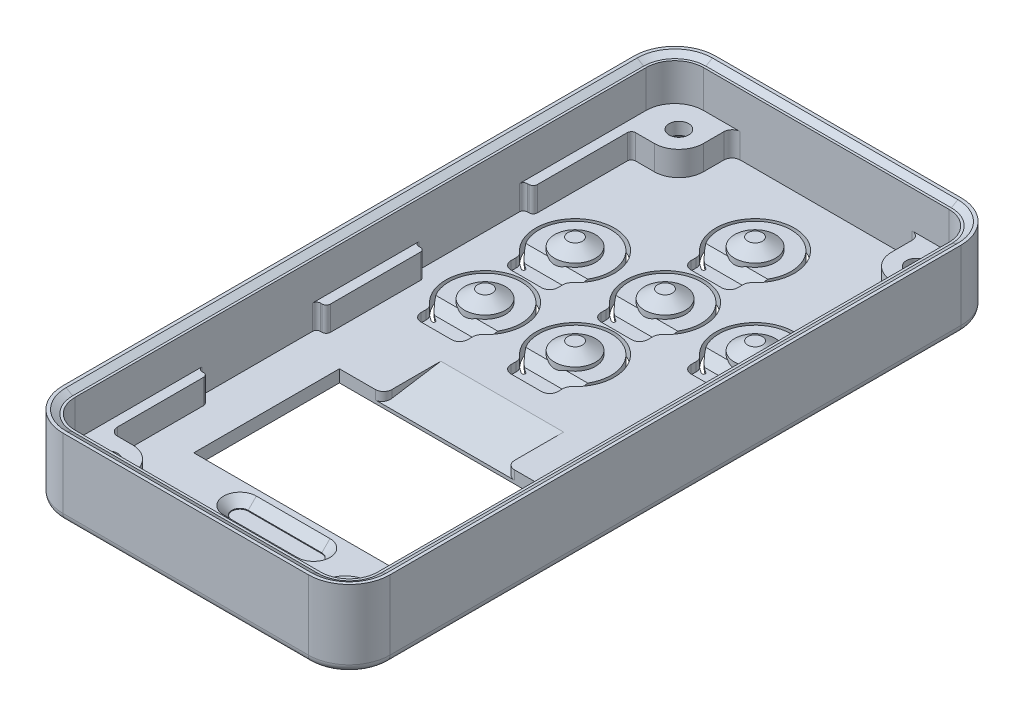
SolidWorks part; units mm, degrees
ref_plane "Front Plane" through (0, 0, 0) normal (0, 0, 1) x (1, 0, 0)
ref_plane "Top Plane" through (0, 0, 0) normal (0, 1, 0) x (1, 0, 0)
ref_plane "Right Plane" through (0, 0, 0) normal (1, 0, 0) x (0, 0, -1)
sketch "Base Sketch" plane through (0, 0, 0) normal (0, 1, 0) x (1, 0, 0)
  line L0 (0, 0) -> (40, 0)
  line L1 (40, 0) -> (40, 79.79)
  line L2 (40, 79.79) -> (0, 79.79)
  line L3 (0, 79.79) -> (0, 0)
extrude "Base" add sketch "Base Sketch" along normal blind 9.5
fillet "Corner Rounds R5" radius 5 4 edges at (0, 4.75, -79.79) (40, 4.75, -79.79) (40, 4.75, 0) (0, 4.75, 0)
shell "Shell 1.5" thickness 1.5 removed face at (20, 9.5, -39.895)
sketch "Boss Sketch" plane through (0, 0, 0) normal (0, 1, 0) x (1, 0, 0)
  line L0 (1.5, 1.5) -> (8.5, 1.5)
  line L1 (8.5, 1.5) -> (8.5, 5)
  line L2 (5.5, 8) -> (1.5, 8)
  line L3 (1.5, 8) -> (1.5, 1.5)
  line L4 (38.5, 1.5) -> (31.5, 1.5)
  line L5 (31.5, 1.5) -> (31.5, 5)
  line L6 (34.5, 8) -> (38.5, 8)
  line L7 (38.5, 8) -> (38.5, 1.5)
  line L16 (1.5, 78.29) -> (8.5, 78.29)
  line L17 (8.5, 78.29) -> (8.5, 74.79)
  line L18 (5.5, 71.79) -> (1.5, 71.79)
  line L19 (1.5, 71.79) -> (1.5, 78.29)
  line L20 (38.5, 78.29) -> (31.5, 78.29)
  line L21 (31.5, 78.29) -> (31.5, 74.79)
  line L22 (34.5, 71.79) -> (38.5, 71.79)
  line L23 (38.5, 71.79) -> (38.5, 78.29)
  arc A0 (8.5, 5) -> (5.5, 8) centre (5.4999, 4.9999) ccw
  circle A1 centre (5.5, 5) radius 1
  arc A2 (31.5, 5) -> (34.5, 8) centre (34.5001, 4.9999) cw
  circle A3 centre (34.5, 5) radius 1
  circle A5 centre (5.5, 74.79) radius 1
  circle A7 centre (34.5, 74.79) radius 1
  arc A8 (8.5, 74.79) -> (5.5, 71.79) centre (5.4999, 74.7901) cw
  arc A9 (31.5, 74.79) -> (34.5, 71.79) centre (34.5001, 74.7901) ccw
extrude "Corner Bosses (stop at ledge y4.5) + M2 Holes" add sketch "Boss Sketch" along normal blind 4.5
sketch "Ledge Sketch" plane through (0, 0, 0) normal (0, 1, 0) x (1, 0, 0)
  line L0 (1.5, 8) -> (2.7, 8)
  line L1 (2.7, 8) -> (2.7, 20)
  line L2 (2.7, 20) -> (1.5, 20)
  line L3 (1.5, 20) -> (1.5, 8)
  line L4 (37.3, 8) -> (38.5, 8)
  line L5 (38.5, 8) -> (38.5, 20)
  line L6 (38.5, 20) -> (37.3, 20)
  line L7 (37.3, 20) -> (37.3, 8)
  line L8 (1.5, 34.5) -> (2.7, 34.5)
  line L9 (2.7, 34.5) -> (2.7, 46.5)
  line L10 (2.7, 46.5) -> (1.5, 46.5)
  line L11 (1.5, 46.5) -> (1.5, 34.5)
  line L12 (37.3, 34.5) -> (38.5, 34.5)
  line L13 (38.5, 34.5) -> (38.5, 46.5)
  line L14 (38.5, 46.5) -> (37.3, 46.5)
  line L15 (37.3, 46.5) -> (37.3, 34.5)
  line L16 (1.5, 59.79) -> (2.7, 59.79)
  line L17 (2.7, 59.79) -> (2.7, 71.79)
  line L18 (2.7, 71.79) -> (1.5, 71.79)
  line L19 (1.5, 71.79) -> (1.5, 59.79)
  line L20 (37.3, 59.79) -> (38.5, 59.79)
  line L21 (38.5, 59.79) -> (38.5, 71.79)
  line L22 (38.5, 71.79) -> (37.3, 71.79)
  line L23 (37.3, 71.79) -> (37.3, 59.79)
extrude "Side Ledges" add sketch "Ledge Sketch" along normal blind 4.5
fillet "Outer Face Round R1" radius 1 8 edges at (1.4645, 0, -1.4645) (20, 0, 0) (38.5355, 0, -1.4645) (40, 0, -39.895) (38.5355, 0, -78.3255) (20, 0, -79.79) (1.4645, 0, -78.3255) (0, 0, -39.895)
sketch "Window Sketch" plane through (0, 0, 0) normal (0, 1, 0) x (1, 0, 0)
  line L0 (7.1, 14.5) -> (32.9, 14.5)
  line L1 (32.9, 14.5) -> (32.9, 31.7)
  line L2 (32.9, 31.7) -> (7.1, 31.7)
  line L3 (7.1, 31.7) -> (7.1, 14.5)
extrude "Display Window" cut sketch "Window Sketch" along normal through all
ref_plane "Mid Plane X20" through (20, 0, 0) normal (1, 0, 0) x (0, 0, -1)
sketch "Ramp Sketch" plane through (20, 0, 0) normal (1, 0, 0) x (0, 0, -1)
  line L0 (31, 0.4) -> (31.7, 0.4)
  line L1 (31.7, 0.4) -> (38.7, 1.5)
  line L2 (38.7, 1.5) -> (38.7, 2.5)
  line L3 (38.7, 2.5) -> (31, 2.5)
  line L4 (31, 2.5) -> (31, 0.4)
extrude "Cable Ramp" cut sketch "Ramp Sketch" against normal blind 7.5 and the other way blind 7.5
ref_plane "Plate Inner Face" through (0, 1.5, 0) normal (0, 1, 0) x (1, 0, 0)
sketch "LED Window Sketch" plane through (0, 1.5, 0) normal (0, 1, 0) x (1, 0, 0)
  circle A0 centre (20, 7.28) radius 1.7
  dimension "D1" = 3.4
extrude "LED Window" cut sketch "LED Window Sketch" against normal blind 1.1
sketch "Plunger Stems Sketch" plane through (0, 1.5, 0) normal (0, 1, 0) x (1, 0, 0)
  circle A0 centre (9, 47.6) radius 2.5
  circle A1 centre (20, 47.6) radius 2.5
  circle A2 centre (9, 58.6) radius 2.5
  circle A3 centre (20, 58.6) radius 2.5
  circle A4 centre (31, 58.6) radius 2.5
  circle A5 centre (20, 69.6) radius 2.5
extrude "Plunger Stems 5.0" add sketch "Plunger Stems Sketch" along normal blind 0.45
ref_plane "Plunger Cone Base" through (0, 1.95, 0) normal (0, 1, 0) x (1, 0, 0)
sketch "Plunger Cone Sketch" plane through (0, 1.95, 0) normal (0, 1, 0) x (1, 0, 0)
  circle A0 centre (9, 47.6) radius 2.5
  circle A1 centre (20, 47.6) radius 2.5
  circle A2 centre (9, 58.6) radius 2.5
  circle A3 centre (20, 58.6) radius 2.5
  circle A4 centre (31, 58.6) radius 2.5
  circle A5 centre (20, 69.6) radius 2.5
extrude "Plunger Cones to 1.8" add sketch "Plunger Cone Sketch" along normal blind 1 draft 57.995
fillet "Boss Junction Fillets R1" radius 1 7 edges at (37.3, 3, -71.79) (37.3, 3, -8) (2.7, 3, -8) (31.5, 3, -78.29) (8.5, 3, -78.29) (31.5, 3, -1.5) (8.5, 3, -1.5)
sketch "C-Slot Sketch" plane through (0, 0, 0) normal (0, 1, 0) x (1, 0, 0)
  arc A0 (10.4434, 43.0222) -> (7.5566, 43.0222) centre (9, 47.6) ccw
  arc A1 (7.5566, 43.0222) -> (7.6769, 43.4036) centre (7.6168, 43.2129) ccw
  arc A2 (7.6769, 43.4036) -> (10.3231, 43.4036) centre (9, 47.6) cw
  arc A3 (10.3231, 43.4036) -> (10.4434, 43.0222) centre (10.3832, 43.2129) ccw
  arc A4 (21.4434, 43.0222) -> (18.5566, 43.0222) centre (20, 47.6) ccw
  arc A5 (18.5566, 43.0222) -> (18.6769, 43.4036) centre (18.6168, 43.2129) ccw
  arc A6 (18.6769, 43.4036) -> (21.3231, 43.4036) centre (20, 47.6) cw
  arc A7 (21.3231, 43.4036) -> (21.4434, 43.0222) centre (21.3832, 43.2129) ccw
  arc A8 (10.4434, 54.0222) -> (7.5566, 54.0222) centre (9, 58.6) ccw
  arc A9 (7.5566, 54.0222) -> (7.6769, 54.4036) centre (7.6168, 54.2129) ccw
  arc A10 (7.6769, 54.4036) -> (10.3231, 54.4036) centre (9, 58.6) cw
  arc A11 (10.3231, 54.4036) -> (10.4434, 54.0222) centre (10.3832, 54.2129) ccw
  arc A12 (21.4434, 54.0222) -> (18.5566, 54.0222) centre (20, 58.6) ccw
  arc A13 (18.5566, 54.0222) -> (18.6769, 54.4036) centre (18.6168, 54.2129) ccw
  arc A14 (18.6769, 54.4036) -> (21.3231, 54.4036) centre (20, 58.6) cw
  arc A15 (21.3231, 54.4036) -> (21.4434, 54.0222) centre (21.3832, 54.2129) ccw
  arc A16 (32.4434, 54.0222) -> (29.5566, 54.0222) centre (31, 58.6) ccw
  arc A17 (29.5566, 54.0222) -> (29.6769, 54.4036) centre (29.6168, 54.2129) ccw
  arc A18 (29.6769, 54.4036) -> (32.3231, 54.4036) centre (31, 58.6) cw
  arc A19 (32.3231, 54.4036) -> (32.4434, 54.0222) centre (32.3832, 54.2129) ccw
  arc A20 (21.4434, 65.0222) -> (18.5566, 65.0222) centre (20, 69.6) ccw
  arc A21 (18.5566, 65.0222) -> (18.6769, 65.4036) centre (18.6168, 65.2129) ccw
  arc A22 (18.6769, 65.4036) -> (21.3231, 65.4036) centre (20, 69.6) cw
  arc A23 (21.3231, 65.4036) -> (21.4434, 65.0222) centre (21.3832, 65.2129) ccw
sketch "Sketch10" plane through (0, 1.5, 0) normal (0, 1, 0) x (1, 0, 0)
  line L0 (11.864, 44.259) -> (11.864, 41.636)
  line L1 (11.864, 41.636) -> (6.136, 41.636)
  line L2 (6.136, 41.636) -> (6.136, 44.259)
  line L3 (6.136, 44.259) -> (11.864, 44.259)
  line L4 (22.864, 44.259) -> (22.864, 41.636)
  line L5 (22.864, 41.636) -> (17.136, 41.636)
  line L6 (17.136, 41.636) -> (17.136, 44.259)
  line L7 (17.136, 44.259) -> (22.864, 44.259)
  line L8 (11.864, 55.259) -> (11.864, 52.636)
  line L9 (11.864, 52.636) -> (6.136, 52.636)
  line L10 (6.136, 52.636) -> (6.136, 55.259)
  line L11 (6.136, 55.259) -> (11.864, 55.259)
  line L12 (22.864, 55.259) -> (22.864, 52.636)
  line L13 (22.864, 52.636) -> (17.136, 52.636)
  line L14 (17.136, 52.636) -> (17.136, 55.259)
  line L15 (17.136, 55.259) -> (22.864, 55.259)
  line L16 (33.864, 55.259) -> (33.864, 52.636)
  line L17 (33.864, 52.636) -> (28.136, 52.636)
  line L18 (28.136, 52.636) -> (28.136, 55.259)
  line L19 (28.136, 55.259) -> (33.864, 55.259)
  line L20 (22.864, 66.259) -> (22.864, 63.636)
  line L21 (22.864, 63.636) -> (17.136, 63.636)
  line L22 (17.136, 63.636) -> (17.136, 66.259)
  line L23 (17.136, 66.259) -> (22.864, 66.259)
extrude "Cut-Extrude7" cut sketch "Sketch10" against normal blind 1.1
sketch "Sketch11" plane through (0, 0, 0) normal (0, 1, 0) x (1, 0, 0)
  arc A0 (11.4, 43.4431) -> (6.6, 43.4431) centre (9, 47.6) ccw
  arc A1 (6.6, 43.4431) -> (6.8, 43.7895) centre (6.7, 43.6163) ccw
  arc A2 (6.8, 43.7895) -> (11.2, 43.7895) centre (9, 47.6) cw
  arc A3 (11.2, 43.7895) -> (11.4, 43.4431) centre (11.3, 43.6163) ccw
  arc A4 (22.4, 43.4431) -> (17.6, 43.4431) centre (20, 47.6) ccw
  arc A5 (17.6, 43.4431) -> (17.8, 43.7895) centre (17.7, 43.6163) ccw
  arc A6 (17.8, 43.7895) -> (22.2, 43.7895) centre (20, 47.6) cw
  arc A7 (22.2, 43.7895) -> (22.4, 43.4431) centre (22.3, 43.6163) ccw
  arc A8 (11.4, 54.4431) -> (6.6, 54.4431) centre (9, 58.6) ccw
  arc A9 (6.6, 54.4431) -> (6.8, 54.7895) centre (6.7, 54.6163) ccw
  arc A10 (6.8, 54.7895) -> (11.2, 54.7895) centre (9, 58.6) cw
  arc A11 (11.2, 54.7895) -> (11.4, 54.4431) centre (11.3, 54.6163) ccw
  arc A12 (22.4, 54.4431) -> (17.6, 54.4431) centre (20, 58.6) ccw
  arc A13 (17.6, 54.4431) -> (17.8, 54.7895) centre (17.7, 54.6163) ccw
  arc A14 (17.8, 54.7895) -> (22.2, 54.7895) centre (20, 58.6) cw
  arc A15 (22.2, 54.7895) -> (22.4, 54.4431) centre (22.3, 54.6163) ccw
  arc A16 (33.4, 54.4431) -> (28.6, 54.4431) centre (31, 58.6) ccw
  arc A17 (28.6, 54.4431) -> (28.8, 54.7895) centre (28.7, 54.6163) ccw
  arc A18 (28.8, 54.7895) -> (33.2, 54.7895) centre (31, 58.6) cw
  arc A19 (33.2, 54.7895) -> (33.4, 54.4431) centre (33.3, 54.6163) ccw
  arc A20 (22.4, 65.4431) -> (17.6, 65.4431) centre (20, 69.6) ccw
  arc A21 (17.6, 65.4431) -> (17.8, 65.7895) centre (17.7, 65.6163) ccw
  arc A22 (17.8, 65.7895) -> (22.2, 65.7895) centre (20, 69.6) cw
  arc A23 (22.2, 65.7895) -> (22.4, 65.4431) centre (22.3, 65.6163) ccw
extrude "Button C-Slots 300deg 0.4" cut sketch "Sketch11" along normal through all
chamfer "Chamfer1" distance 1.1 angle 45 6 edges at (9, 1.5, -44.259) (20, 1.5, -66.259) (31, 1.5, -55.259) (20, 1.5, -55.259) (9, 1.5, -55.259) (20, 1.5, -44.259)
fillet "Fillet1" radius 1 24 edges at (11.864, 0.95, -43.7481) (11.864, 0.95, -41.636) (6.136, 0.95, -41.636) (6.136, 0.95, -43.7481) (22.864, 0.95, -63.636) (22.864, 0.95, -65.7481) (17.136, 0.95, -63.636) (17.136, 0.95, -65.7481) (33.864, 0.95, -52.636) (33.864, 0.95, -54.7481) (28.136, 0.95, -52.636) (28.136, 0.95, -54.7481) (22.864, 0.95, -52.636) (22.864, 0.95, -54.7481) (17.136, 0.95, -52.636) (17.136, 0.95, -54.7481) (11.864, 0.95, -52.636) (11.864, 0.95, -54.7481) (6.136, 0.95, -52.636) (6.136, 0.95, -54.7481) (22.864, 0.95, -41.636) (22.864, 0.95, -43.7481) (17.136, 0.95, -41.636) (17.136, 0.95, -43.7481)
fillet "Fillet2" radius 0.5 17 edges at (2.7, 3, -71.79) (1.5, 3, -59.79) (2.7, 3, -59.79) (38.5, 3, -59.79) (37.3, 3, -59.79) (38.5, 3, -46.5) (37.3, 3, -46.5) (2.7, 3, -46.5) (1.5, 3, -46.5) (38.5, 3, -34.5) (37.3, 3, -34.5) (2.7, 3, -34.5) (1.5, 3, -34.5) (38.5, 3, -20) (37.3, 3, -20) (2.7, 3, -20) (1.5, 3, -20)
fillet "Fillet3" radius 1 2 edges at (27.5, 0.95, -31.7) (12.5, 0.95, -31.7)
sketch "Button Symbols Cut Sketch" plane through (0, 0, 0) normal (0, 1, 0) x (1, 0, 0)
  line L0 (7.0908, 45.6908) -> (7.7272, 46.3272)
  line L1 (10.2728, 46.3272) -> (10.9092, 45.6908)
  line L2 (8.55, 47.2) -> (9.45, 47.2)
  line L3 (9.45, 47.2) -> (9.45, 44.4)
  line L4 (9.45, 44.4) -> (8.55, 44.4)
  line L5 (8.55, 44.4) -> (8.55, 47.2)
  line L6 (20, 44.8) -> (22.4249, 49)
  line L7 (22.4249, 49) -> (17.5751, 49)
  line L8 (17.5751, 49) -> (20, 44.8)
  line L9 (6.2, 58.6) -> (10.4, 56.1751)
  line L10 (10.4, 56.1751) -> (10.4, 61.0249)
  line L11 (10.4, 61.0249) -> (6.2, 58.6)
  line L12 (33.8, 58.6) -> (29.6, 61.0249)
  line L13 (29.6, 61.0249) -> (29.6, 56.1751)
  line L14 (29.6, 56.1751) -> (33.8, 58.6)
  line L15 (20, 72.4) -> (17.5751, 68.2)
  line L16 (17.5751, 68.2) -> (22.4249, 68.2)
  line L17 (22.4249, 68.2) -> (20, 72.4)
  arc A0 (10.9092, 45.6908) -> (7.0908, 45.6908) centre (9, 47.6) ccw
  arc A1 (7.7272, 46.3272) -> (10.2728, 46.3272) centre (9, 47.6) cw
  circle A2 centre (20, 58.6) radius 2.4
  circle A3 centre (20, 58.6) radius 1.5
sketch "Button Symbols Inlay Sketch" plane through (0, 0, 0) normal (0, 1, 0) x (1, 0, 0)
  line L0 (7.0908, 45.6908) -> (7.7272, 46.3272)
  line L1 (10.2728, 46.3272) -> (10.9092, 45.6908)
  line L2 (8.55, 47.2) -> (9.45, 47.2)
  line L3 (9.45, 47.2) -> (9.45, 44.4)
  line L4 (9.45, 44.4) -> (8.55, 44.4)
  line L5 (8.55, 44.4) -> (8.55, 47.2)
  line L6 (20, 44.8) -> (22.4249, 49)
  line L7 (22.4249, 49) -> (17.5751, 49)
  line L8 (17.5751, 49) -> (20, 44.8)
  line L9 (6.2, 58.6) -> (10.4, 56.1751)
  line L10 (10.4, 56.1751) -> (10.4, 61.0249)
  line L11 (10.4, 61.0249) -> (6.2, 58.6)
  line L12 (33.8, 58.6) -> (29.6, 61.0249)
  line L13 (29.6, 61.0249) -> (29.6, 56.1751)
  line L14 (29.6, 56.1751) -> (33.8, 58.6)
  line L15 (20, 72.4) -> (17.5751, 68.2)
  line L16 (17.5751, 68.2) -> (22.4249, 68.2)
  line L17 (22.4249, 68.2) -> (20, 72.4)
  arc A0 (10.9092, 45.6908) -> (7.0908, 45.6908) centre (9, 47.6) ccw
  arc A1 (7.7272, 46.3272) -> (10.2728, 46.3272) centre (9, 47.6) cw
  circle A2 centre (20, 58.6) radius 2.4
  circle A3 centre (20, 58.6) radius 1.5
sketch "Sketch14" plane through (0, 0, 0) normal (0, 1, 0) x (1, 0, 0)
  line L0 (8.4, 47) -> (8.4, 45.2)
  line L1 (9.6, 45.2) -> (9.6, 47)
  line L2 (20.5196, 44.9) -> (22.7713, 48.8)
  line L3 (22.2517, 49.7) -> (17.7483, 49.7)
  line L4 (17.2287, 48.8) -> (19.4804, 44.9)
  line L5 (6.1, 58.0804) -> (10, 55.8287)
  line L6 (10.9, 56.3483) -> (10.9, 60.8517)
  line L7 (10, 61.3713) -> (6.1, 59.1196)
  line L8 (33.9, 59.1196) -> (30, 61.3713)
  line L9 (29.1, 60.8517) -> (29.1, 56.3483)
  line L10 (30, 55.8287) -> (33.9, 58.0804)
  line L11 (19.4804, 72.5) -> (17.2287, 68.6)
  line L12 (17.7483, 67.7) -> (22.2517, 67.7)
  line L13 (22.7713, 68.6) -> (20.5196, 72.5)
  arc A0 (11.4513, 45.5431) -> (6.5487, 45.5431) centre (9, 47.6) ccw
  arc A1 (6.5487, 45.5431) -> (7.4679, 46.3144) centre (7.0083, 45.9288) ccw
  arc A2 (7.4679, 46.3144) -> (10.5321, 46.3144) centre (9, 47.6) cw
  arc A3 (10.5321, 46.3144) -> (11.4513, 45.5431) centre (10.9917, 45.9288) ccw
  arc A4 (8.4, 45.2) -> (9.6, 45.2) centre (9, 45.2) ccw
  arc A5 (9.6, 47) -> (8.4, 47) centre (9, 47) ccw
  arc A6 (19.4804, 44.9) -> (20.5196, 44.9) centre (20, 45.2) ccw
  arc A7 (22.7713, 48.8) -> (22.2517, 49.7) centre (22.2517, 49.1) ccw
  arc A8 (17.7483, 49.7) -> (17.2287, 48.8) centre (17.7483, 49.1) ccw
  arc A9 (6.1, 59.1196) -> (6.1, 58.0804) centre (6.4, 58.6) ccw
  arc A10 (10, 55.8287) -> (10.9, 56.3483) centre (10.3, 56.3483) ccw
  arc A11 (10.9, 60.8517) -> (10, 61.3713) centre (10.3, 60.8517) ccw
  circle A12 centre (20, 58.6) radius 3.1
  circle A13 centre (20, 58.6) radius 1.9
  arc A14 (33.9, 58.0804) -> (33.9, 59.1196) centre (33.6, 58.6) ccw
  arc A15 (30, 61.3713) -> (29.1, 60.8517) centre (29.7, 60.8517) ccw
  arc A16 (29.1, 56.3483) -> (30, 55.8287) centre (29.7, 56.3483) ccw
  arc A17 (20.5196, 72.5) -> (19.4804, 72.5) centre (20, 72.2) ccw
  arc A18 (17.2287, 68.6) -> (17.7483, 67.7) centre (17.7483, 68.3) ccw
  arc A19 (22.2517, 67.7) -> (22.7713, 68.6) centre (22.2517, 68.3) ccw
extrude "Button Symbol Recess 0.4" cut sketch "Sketch14" along normal blind 0.4
sketch "Sketch15" plane through (0, 0, 0) normal (0, 1, 0) x (1, 0, 0)
  line L0 (8.4, 47) -> (8.4, 45.2)
  line L1 (9.6, 45.2) -> (9.6, 47)
  line L2 (20.5196, 44.9) -> (22.7713, 48.8)
  line L3 (22.2517, 49.7) -> (17.7483, 49.7)
  line L4 (17.2287, 48.8) -> (19.4804, 44.9)
  line L5 (6.1, 58.0804) -> (10, 55.8287)
  line L6 (10.9, 56.3483) -> (10.9, 60.8517)
  line L7 (10, 61.3713) -> (6.1, 59.1196)
  line L8 (33.9, 59.1196) -> (30, 61.3713)
  line L9 (29.1, 60.8517) -> (29.1, 56.3483)
  line L10 (30, 55.8287) -> (33.9, 58.0804)
  line L11 (19.4804, 72.5) -> (17.2287, 68.6)
  line L12 (17.7483, 67.7) -> (22.2517, 67.7)
  line L13 (22.7713, 68.6) -> (20.5196, 72.5)
  arc A0 (11.4513, 45.5431) -> (6.5487, 45.5431) centre (9, 47.6) ccw
  arc A1 (6.5487, 45.5431) -> (7.4679, 46.3144) centre (7.0083, 45.9288) ccw
  arc A2 (7.4679, 46.3144) -> (10.5321, 46.3144) centre (9, 47.6) cw
  arc A3 (10.5321, 46.3144) -> (11.4513, 45.5431) centre (10.9917, 45.9288) ccw
  arc A4 (8.4, 45.2) -> (9.6, 45.2) centre (9, 45.2) ccw
  arc A5 (9.6, 47) -> (8.4, 47) centre (9, 47) ccw
  arc A6 (19.4804, 44.9) -> (20.5196, 44.9) centre (20, 45.2) ccw
  arc A7 (22.7713, 48.8) -> (22.2517, 49.7) centre (22.2517, 49.1) ccw
  arc A8 (17.7483, 49.7) -> (17.2287, 48.8) centre (17.7483, 49.1) ccw
  arc A9 (6.1, 59.1196) -> (6.1, 58.0804) centre (6.4, 58.6) ccw
  arc A10 (10, 55.8287) -> (10.9, 56.3483) centre (10.3, 56.3483) ccw
  arc A11 (10.9, 60.8517) -> (10, 61.3713) centre (10.3, 60.8517) ccw
  circle A12 centre (20, 58.6) radius 3.1
  circle A13 centre (20, 58.6) radius 1.9
  arc A14 (33.9, 58.0804) -> (33.9, 59.1196) centre (33.6, 58.6) ccw
  arc A15 (30, 61.3713) -> (29.1, 60.8517) centre (29.7, 60.8517) ccw
  arc A16 (29.1, 56.3483) -> (30, 55.8287) centre (29.7, 56.3483) ccw
  arc A17 (20.5196, 72.5) -> (19.4804, 72.5) centre (20, 72.2) ccw
  arc A18 (17.2287, 68.6) -> (17.7483, 67.7) centre (17.7483, 68.3) ccw
  arc A19 (22.2517, 67.7) -> (22.7713, 68.6) centre (22.2517, 68.3) ccw
extrude "Button Symbol Inlays 0.4 (colour 2)" add sketch "Sketch15" along normal blind 0.4 separate body
sketch "I2C Header Pocket Sketch" plane through (0, 1.5, 0) normal (0, 1, 0) x (1, 0, 0)
  line L0 (15.5, 9.4) -> (24.5, 9.4)
  line L1 (25.5, 10.4) -> (25.5, 11.9)
  line L2 (24.5, 12.9) -> (15.5, 12.9)
  line L3 (14.5, 11.9) -> (14.5, 10.4)
  line L4 (32.9, 14.5) -> (7.1, 14.5) construction
  arc A0 (24.5, 9.4) -> (25.5, 10.4) centre (24.5, 10.4) ccw
  arc A1 (25.5, 11.9) -> (24.5, 12.9) centre (24.5, 11.9) ccw
  arc A2 (15.5, 12.9) -> (14.5, 11.9) centre (15.5, 11.9) ccw
  arc A3 (14.5, 10.4) -> (15.5, 9.4) centre (15.5, 10.4) ccw
  dimension "D3" = 1
  dimension "D1" = 1.6
  dimension "D2" = 11
  dimension "D4" = 2.6
sketch "Sketch17" plane through (0, 1.5, 0) normal (0, 1, 0) x (1, 0, 0)
  line L0 (15.2, 10.45) -> (24.8, 10.45)
  line L1 (24.8, 11.85) -> (15.2, 11.85)
  arc A0 (24.8, 10.45) -> (24.8, 11.85) centre (24.8, 11.15) ccw
  arc A1 (15.2, 11.85) -> (15.2, 10.45) centre (15.2, 11.15) ccw
sketch "Sketch18" plane through (0, 0, -14.5) normal (0, 0, -1) x (-1, 0, 0)
  line L4 (-32.9, 1.5) -> (-32.9, 0)
  line L5 (-32.9, 0) -> (-7.1, 0)
  line L6 (-7.1, 0) -> (-7.1, 1.5)
  line L7 (-7.1, 1.5) -> (-32.9, 1.5)
  line L8 (-32.9, 1.5) -> (-32.9, 0)
  line L9 (-32.9, 0) -> (-7.1, 0)
  line L10 (-7.1, 0) -> (-7.1, 1.5)
  line L11 (-7.1, 1.5) -> (-32.9, 1.5)
  dimension "D1" = 0
extrude "Cut-Extrude16" cut sketch "Sketch18" against normal blind 0.6
sketch "Sketch19" plane through (0, 1.5, 0) normal (0, 1, 0) x (1, 0, 0)
  line L0 (15.2999, 10.35) -> (24.7001, 10.35)
  line L1 (25.5, 11.1499) -> (25.5, 11.1501)
  line L2 (24.7001, 11.95) -> (15.2999, 11.95)
  line L3 (14.5, 11.1501) -> (14.5, 11.1499)
  arc A0 (24.7001, 10.35) -> (25.5, 11.1499) centre (24.7001, 11.1499) ccw
  arc A1 (25.5, 11.1501) -> (24.7001, 11.95) centre (24.7001, 11.1501) ccw
  arc A2 (15.2999, 11.95) -> (14.5, 11.1501) centre (15.2999, 11.1501) ccw
  arc A3 (14.5, 11.1499) -> (15.2999, 10.35) centre (15.2999, 11.1499) ccw
sketch "Sketch20" plane through (0, 1.5, 0) normal (0, 1, 0) x (1, 0, 0)
  line L0 (15.5, 10.15) -> (24.5, 10.15)
  line L1 (24.5, 12.15) -> (15.5, 12.15)
  arc A0 (24.5, 10.15) -> (24.5, 12.15) centre (24.5, 11.15) ccw
  arc A1 (15.5, 12.15) -> (15.5, 10.15) centre (15.5, 11.15) ccw
extrude "I2C Header Lead Pocket 2.0 (0.2 skin)" cut sketch "Sketch20" against normal blind 1.1
chamfer "Chamfer3" distance 1 angle 45 4 edges at (20, 1.5, -12.15) (14.5, 1.5, -11.15) (25.5, 1.5, -11.15) (20, 1.5, -10.15)
sketch "Sketch21" plane through (0, 0, 0) normal (0, -1, 0) x (1, 0, 0)
  circle A0 centre (20, -7.28) radius 2.5
  circle A1 centre (20, -7.28) radius 1.7
  circle A2 centre (20, -7.28) radius 1.7 construction
  circle A3 centre (20, -7.28) radius 2.6
  dimension "D2" = 5
  dimension "D3" = 0.1
  dimension "D1" = 0
extrude "Cut-Extrude17" cut sketch "Sketch21" against normal blind 0.1
sketch "M2 Clearance 2.4 (screw from front) Sketch" plane through (0, 0, 0) normal (0, 1, 0) x (1, 0, 0)
  circle A0 centre (5.5, 5) radius 1.2
  circle A1 centre (34.5, 5) radius 1.2
  circle A2 centre (5.5, 74.79) radius 1.2
  circle A3 centre (34.5, 74.79) radius 1.2
extrude "M2 Clearance 2.4 (screw from front)" cut sketch "M2 Clearance 2.4 (screw from front) Sketch" along normal through all
sketch "M2 Head Counterbore 4.4 x 2.0 Sketch" plane through (0, 0, 0) normal (0, 1, 0) x (1, 0, 0)
  circle A0 centre (5.5, 5) radius 2.2
  circle A1 centre (34.5, 5) radius 2.2
  circle A2 centre (5.5, 74.79) radius 2.2
  circle A3 centre (34.5, 74.79) radius 2.2
extrude "M2 Head Counterbore 4.4 x 3.0 (8 mm screws)" cut sketch "M2 Head Counterbore 4.4 x 2.0 Sketch" along normal blind 3
chamfer "M2 CSK Seats (head 2 mm below face)" distance 1 angle 45 4 edges at (34.5, 3, -72.59) (5.5, 3, -72.59) (34.5, 3, -2.8) (5.5, 3, -2.8)
ref_plane "Joint Bevel Plane" through (0, 9.0381, 0) normal (0, 1, 0) x (1, 0, 0)
sketch "Wall Bevel 30deg + 0.4 flats Sketch" plane through (0, 9.0381, 0) normal (0, 1, 0) x (1, 0, 0)
  line L0 (5, 1.2) -> (35, 1.2)
  line L1 (38.8, 5) -> (38.8, 74.79)
  line L2 (35, 78.59) -> (5, 78.59)
  line L3 (1.2, 74.79) -> (1.2, 5)
  arc A0 (35, 1.2) -> (38.8, 5) centre (35, 5) ccw
  arc A1 (38.8, 74.79) -> (35, 78.59) centre (35, 74.79) ccw
  arc A2 (5, 78.59) -> (1.2, 74.79) centre (5, 74.79) ccw
  arc A3 (1.2, 5) -> (5, 1.2) centre (5, 5) ccw
extrude "Wall Bevel 30deg + 0.4 flats" cut sketch "Wall Bevel 30deg + 0.4 flats Sketch" along normal blind 0.4619 draft 60 draft outward yes
